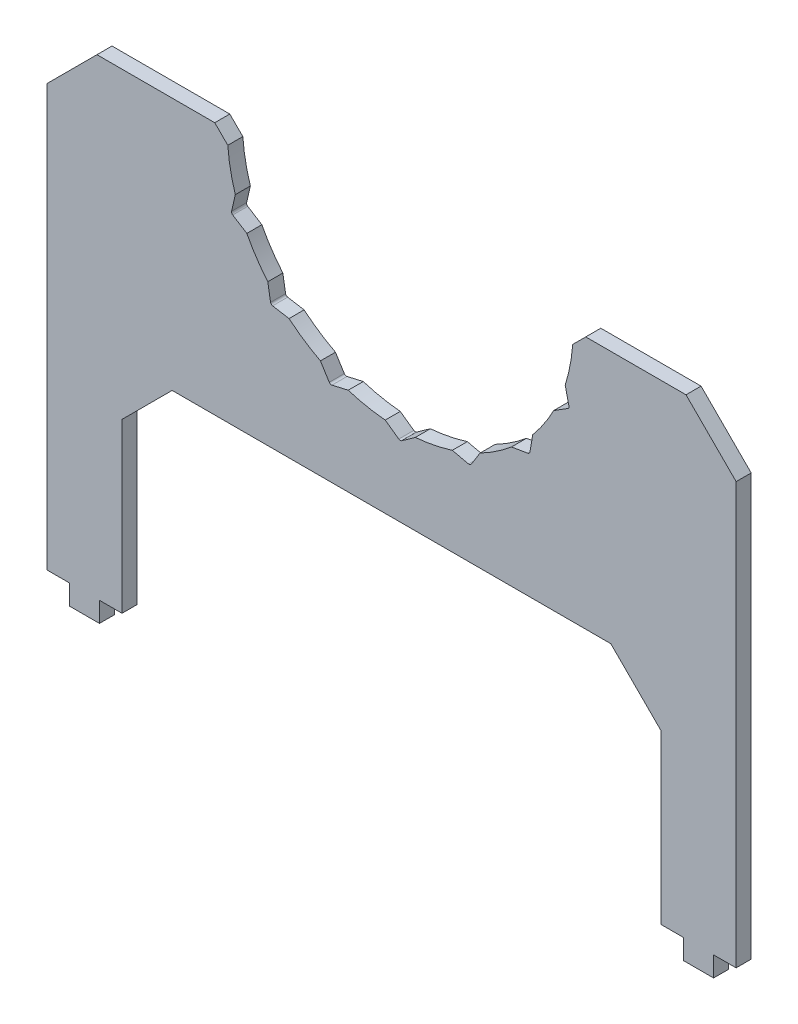
SolidWorks part; units mm, degrees
ref_plane "Front Plane" through (0, 0, 0) normal (0, 0, 1) x (1, 0, 0)
ref_plane "Top Plane" through (0, 0, 0) normal (0, 1, 0) x (1, 0, 0)
ref_plane "Right Plane" through (0, 0, 0) normal (1, 0, 0) x (0, 0, -1)
sketch "Sketch1" plane through (0, 0, 0) normal (0, 0, 1) x (1, 0, 0)
  line L0 (0, 49) -> (0, -49) construction
  line L1 (-68.75, -49) -> (68.75, -49)
  line L2 (-68.75, -49) -> (-68.75, 49)
  line L3 (-68.75, 49) -> (68.75, 49)
  line L4 (68.75, -49) -> (68.75, 49)
  point P6 (0, 0)
  dimension "D1" = 137.5
  dimension "D2" = 98
extrude "Boss-Extrude1" add sketch "Sketch1" along normal mid plane 3
sketch "Sketch2" plane through (0, 0, 1.5) normal (0, 0, 1) x (1, 0, 0)
  line L3 (-53.75, -49) -> (-53.75, -1.5)
  line L4 (-53.75, -1.5) -> (53.75, -1.5)
  line L5 (53.75, -49) -> (53.75, -1.5)
  line L6 (0, 0) -> (0, -1.5) construction
  line L7 (-68.75, 49) -> (-68.75, -49) construction
  line L8 (68.75, -49) -> (68.75, 49) construction
  line L9 (68.75, 49) -> (-68.75, 49) construction
  line L10 (-68.75, -49) -> (68.75, -49) construction
  line L15 (53.75, -49) -> (-53.75, -49)
  line L16 (-68.75, -49) -> (68.75, -49) construction
  circle A0 centre (1.75, 49) radius 34
  dimension "D1" = 68
  dimension "D2" = 15
  dimension "D3" = 47.5
  dimension "D4" = 67
extrude "Cut-Extrude1" cut sketch "Sketch2" against normal through all
sketch "Sketch17" plane through (0, 0, 1.5) normal (0, 0, 1) x (1, 0, 0)
  line L14 (1.75, 49) -> (1.75, 12.5) construction
  line L15 (1.75, 12.5) -> (-1.25, 14.6307)
  line L16 (1.75, 12.5) -> (4.75, 14.6307)
  line L17 (1.75, 49) -> (15.7179, 15.2784) construction
  line L18 (15.7179, 15.2784) -> (12.1309, 16.0988)
  line L19 (15.7179, 15.2784) -> (17.6742, 18.3949)
  line L20 (1.75, 49) -> (27.5594, 23.1906) construction
  line L22 (27.5594, 23.1906) -> (28.1741, 26.8185)
  line L24 (27.5594, 23.1906) -> (23.9315, 22.5759)
  line L26 (1.75, 49) -> (35.4716, 35.0321) construction
  line L27 (35.4716, 35.0321) -> (34.6512, 38.6191)
  line L28 (35.4716, 35.0321) -> (32.3551, 33.0758)
  line L29 (1.75, 49) -> (-12.2179, 15.2784) construction
  line L30 (1.75, 49) -> (-24.0594, 23.1906) construction
  line L31 (1.75, 49) -> (-31.9716, 35.0321) construction
  line L32 (-12.2179, 15.2784) -> (-14.1742, 18.3949)
  line L33 (-12.2179, 15.2784) -> (-8.6309, 16.0988)
  line L34 (-24.0594, 23.1906) -> (-24.6741, 26.8185)
  line L35 (-24.0594, 23.1906) -> (-20.4315, 22.5759)
  line L36 (-31.9716, 35.0321) -> (-31.1512, 38.6191)
  line L37 (-31.9716, 35.0321) -> (-28.8551, 33.0758)
  arc A2 (17.6742, 18.3949) -> (23.9315, 22.5759) centre (1.75, 49) ccw
  circle A12 centre (1.75, 49) radius 36.5 construction
  arc A14 (4.75, 14.6307) -> (12.1309, 16.0988) centre (1.75, 49) ccw
  arc A16 (28.1741, 26.8185) -> (32.3551, 33.0758) centre (1.75, 49) ccw
  arc A17 (34.6512, 38.6191) -> (-31.1512, 38.6191) centre (1.75, 49) ccw
  arc A18 (-8.6309, 16.0988) -> (-1.25, 14.6307) centre (1.75, 49) ccw
  arc A19 (-20.4315, 22.5759) -> (-14.1742, 18.3949) centre (1.75, 49) ccw
  arc A20 (-28.8551, 33.0758) -> (-24.6741, 26.8185) centre (1.75, 49) ccw
  dimension "D1" = 73
  dimension "D2" = 69
  dimension "D3" = 6
  dimension "D4" = 22.5
  dimension "D5" = 6
  dimension "D6" = 6
  dimension "D7" = 22.5
  dimension "D8" = 6
  dimension "D9" = 22.5
  dimension "D10" = 6
  dimension "D11" = 6
  dimension "D12" = 6
  dimension "D13" = 22.5
  dimension "D14" = 22.5
  dimension "D15" = 22.5
extrude "Cut-Extrude3" cut sketch "Sketch17" against normal through all
fillet "Fillet1" radius 0.5 7 edges at (-31.9716, 35.0321, 0) (-12.2179, 15.2784, 0) (-24.0594, 23.1906, 0) (1.75, 12.5, 0) (15.7179, 15.2784, 0) (27.5594, 23.1906, 0) (35.4716, 35.0321, 0)
sketch "Sketch22" plane through (0, 0, -1.5) normal (0, 0, -1) x (-1, 0, 0)
  line L1 (-68.75, -49) -> (-64.25, -49)
  line L2 (-68.75, -49) -> (-68.75, -45)
  line L3 (-68.75, -45) -> (-64.25, -45)
  line L4 (-64.25, -49) -> (-64.25, -45)
  line L6 (64.25, -49) -> (68.75, -49)
  line L7 (64.25, -49) -> (64.25, -45)
  line L8 (64.25, -45) -> (68.75, -45)
  line L9 (68.75, -49) -> (68.75, -45)
  line L10 (-68.75, -49) -> (-68.75, 49) construction
  line L12 (68.75, -49) -> (53.75, -49) construction
  line L13 (-53.75, -49) -> (-68.75, -49) construction
  line L14 (53.75, -49) -> (58.25, -49)
  line L15 (53.75, -49) -> (53.75, -45)
  line L16 (53.75, -45) -> (58.25, -45)
  line L17 (58.25, -49) -> (58.25, -45)
  line L18 (-53.75, -49) -> (-58.25, -49)
  line L19 (-53.75, -49) -> (-53.75, -45)
  line L20 (-53.75, -45) -> (-58.25, -45)
  line L21 (-58.25, -49) -> (-58.25, -45)
  dimension "D1" = 6
  dimension "D2" = 4
extrude "Cut-Extrude5" cut sketch "Sketch22" against normal through all
chamfer "Chamfer1" distance 10 angle 45 4 edges at (-53.75, -1.5, 0) (53.75, -1.5, 0) (-68.75, 49, 0) (68.75, 49, 0)
chamfer "Chamfer2" distance 2.5 angle 45 2 edges at (-32.75, 49, 0) (36.25, 49, 0)
